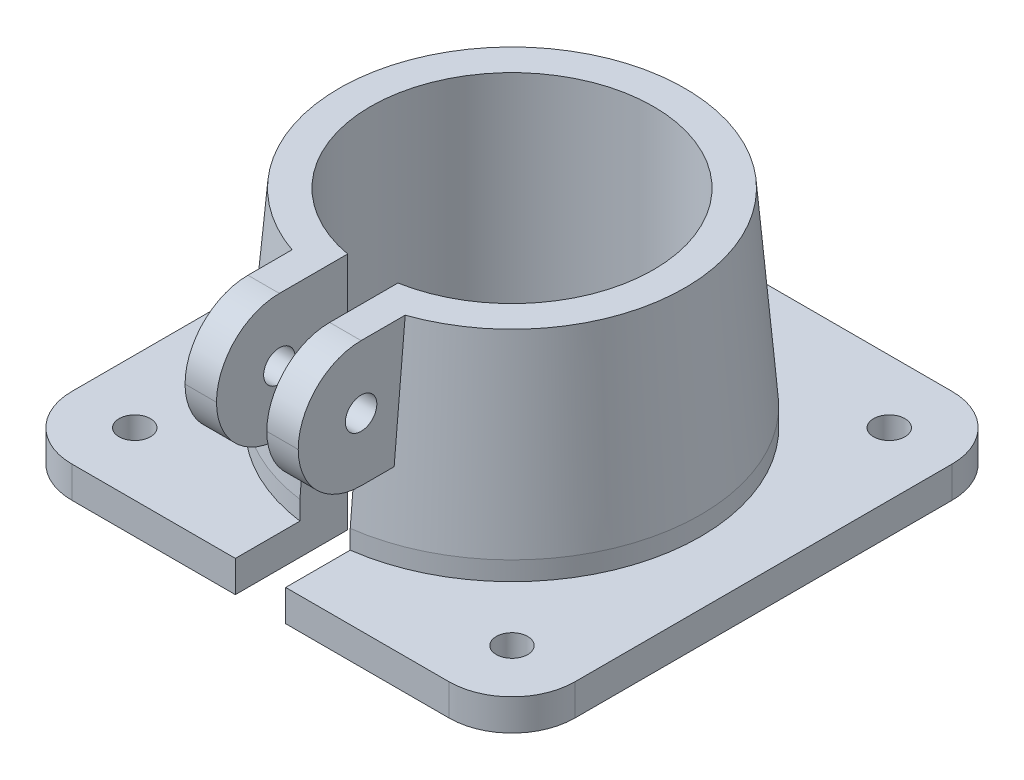
SolidWorks part; units mm, degrees
ref_plane "Front Plane" through (0, 0, 0) normal (0, 0, 1) x (1, 0, 0)
ref_plane "Top Plane" through (0, 0, 0) normal (0, 1, 0) x (1, 0, 0)
ref_plane "Right Plane" through (0, 0, 0) normal (1, 0, 0) x (0, 0, -1)
sketch "Sketch1" plane through (0, 0, 0) normal (0, 1, 0) x (1, 0, 0)
  line L1 (30, -40) -> (-30, -40)
  line L2 (40, -30) -> (40, 30)
  line L3 (30, 40) -> (-30, 40)
  line L4 (-40, -30) -> (-40, 30)
  line L5 (40, -40) -> (-40, 40) construction
  line L6 (40, 40) -> (-40, -40) construction
  arc A0 (30, -40) -> (40, -30) centre (30, -30) ccw
  arc A1 (-30, -40) -> (-40, -30) centre (-30, -30) cw
  arc A2 (40, 30) -> (30, 40) centre (30, 30) ccw
  arc A3 (-40, 30) -> (-30, 40) centre (-30, 30) cw
  point P0 (0, 0)
  dimension "D2" = 10
  dimension "D1" = 80
extrude "Boss-Extrude1" add sketch "Sketch1" along normal blind 5
sketch "Sketch2" plane through (0, 5, 0) normal (0, 1, 0) x (1, 0, 0)
  circle A0 centre (0, 0) radius 30
  dimension "D1" = 60
extrude "Boss-Extrude2" add sketch "Sketch2" along normal blind 3
sketch "Sketch3" plane through (0, 8, 0) normal (0, 1, 0) x (1, 0, 0)
  circle A0 centre (0, 0) radius 27.5
  dimension "D1" = 55
extrude "Boss-Extrude3" add sketch "Sketch3" along normal blind 30
sketch "Sketch4" plane through (0, 38, 0) normal (0, 1, 0) x (1, 0, 0)
  circle A0 centre (0, 0) radius 22.5
  dimension "D1" = 45
extrude "Cut-Extrude1" cut sketch "Sketch4" against normal through all
loft "Loft1" add section edge at (0, 8, 30) section edge at (0, 38, 27.5) connector at (-24.738, 8, -16.9715) connector at (-23.7666, 38, -13.8347)
sketch "Sketch6" plane through (0, 38, 0) normal (0, 1, 0) x (1, 0, 0)
  circle A0 centre (0, 0) radius 22.5
  dimension "D1" = 45
extrude "Cut-Extrude2" cut sketch "Sketch6" against normal through all
sketch "Sketch7" plane through (0, 0, 0) normal (0, 1, 0) x (1, 0, 0)
  line L0 (-30, -40) -> (30, -40) construction
  line L1 (-4, -12.5327) -> (4, -12.5327)
  line L2 (-4, -12.5327) -> (-4, -40)
  line L3 (-4, -40) -> (4, -40)
  line L4 (4, -12.5327) -> (4, -40)
  point P6 (0, -12.5327)
  dimension "D1" = 8
extrude "Cut-Extrude5" cut sketch "Sketch7" against normal blind 13 and the other way through all contours L2 L1 L4 L3
sketch "Sketch8" plane through (0, 0, 0) normal (0, 0, 1) x (1, 0, 0)
  line L1 (-4, 38) -> (-9, 38)
  line L2 (-4, 38) -> (-4, 18)
  line L3 (-4, 18) -> (-9, 18)
  line L4 (-9, 38) -> (-9, 18)
  line L5 (4, 38) -> (9, 38)
  line L6 (4, 38) -> (4, 18)
  line L7 (4, 18) -> (9, 18)
  line L8 (9, 38) -> (9, 18)
  dimension "D1" = 5
  dimension "D2" = 5
  dimension "D3" = 20
extrude "Boss-Extrude4" add sketch "Sketch8" along normal blind 43
fillet "Fillet1" radius 10 4 edges at (6.5, 18, 43) (-6.5, 18, 43) (6.5, 38, 43) (-6.5, 38, 43)
sketch "Sketch9" plane through (9, 0, 0) normal (1, 0, 0) x (0, 0, -1)
  circle A0 centre (-33, 28) radius 2.5
  dimension "D1" = 5
extrude "Cut-Extrude6" cut sketch "Sketch9" against normal blind 43
sketch "Sketch10" plane through (0, 38, 0) normal (0, 1, 0) x (1, 0, 0)
  circle A0 centre (0, 0) radius 22.5
extrude "Cut-Extrude7" cut sketch "Sketch10" against normal blind 43
sketch "Sketch11" plane through (0, 5, 0) normal (0, 1, 0) x (1, 0, 0)
  circle A0 centre (30, -30) radius 2.5
  circle A1 centre (-30, -30) radius 2.5
  circle A2 centre (30, 30) radius 2.5
  circle A3 centre (-30, 30) radius 2.5
  dimension "D1" = 5
extrude "Cut-Extrude8" cut sketch "Sketch11" against normal blind 10
